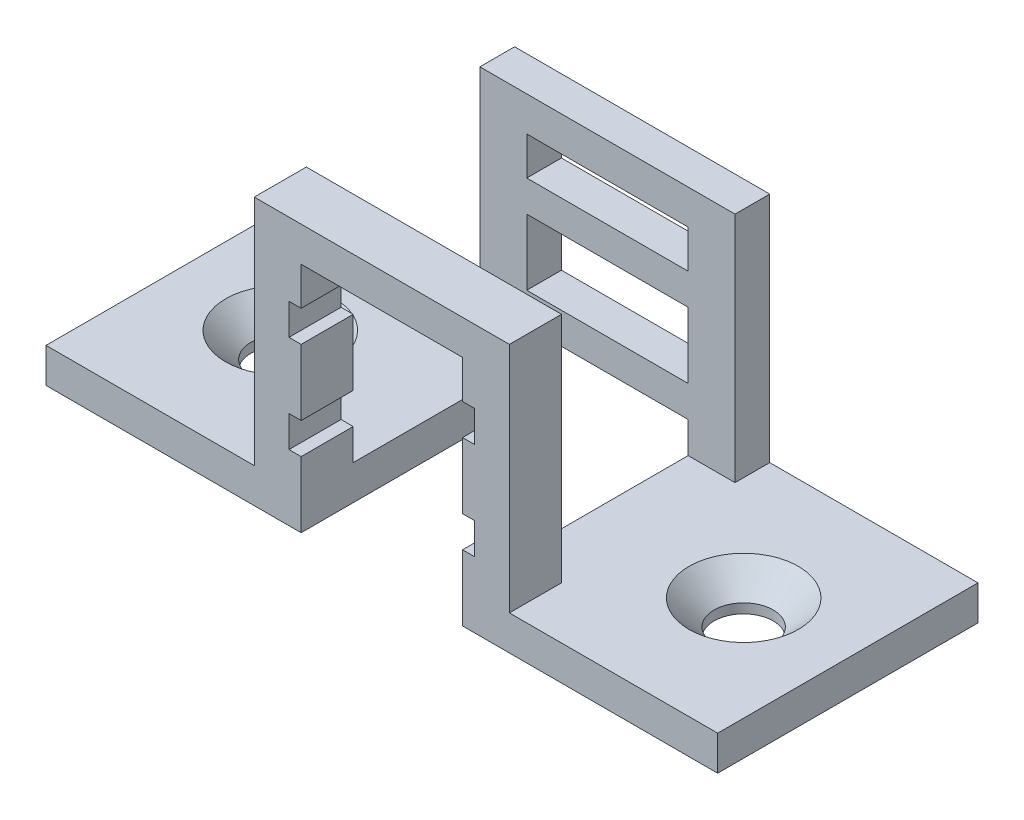
SolidWorks part; units mm, degrees
ref_plane "Front Plane" through (0, 0, 0) normal (0, 0, 1) x (1, 0, 0)
ref_plane "Top Plane" through (0, 0, 0) normal (0, 1, 0) x (1, 0, 0)
ref_plane "Right Plane" through (0, 0, 0) normal (1, 0, 0) x (0, 0, -1)
sketch "Sketch1" plane through (0, 0, 0) normal (0, 1, 0) x (1, 0, 0)
  line L1 (-7.35, -7.5) -> (7.35, -7.5)
  line L2 (-7.35, -7.5) -> (-7.35, 7.5)
  line L3 (-7.35, 7.5) -> (7.35, 7.5)
  line L4 (7.35, -7.5) -> (7.35, 7.5)
  line L5 (-7.35, -7.5) -> (7.35, 7.5) construction
  line L6 (-7.35, 7.5) -> (7.35, -7.5) construction
  point P0 (0, 0)
  dimension "D1" = 15
  dimension "D2" = 14.7
extrude "Boss-Extrude1" add sketch "Sketch1" along normal blind 15.4
sketch "Sketch2" plane through (0, 0, 7.5) normal (0, 0, 1) x (1, 0, 0)
  line L1 (-5.35, -1.2841) -> (5.35, -1.2841)
  line L2 (-5.35, -1.2841) -> (-5.35, 13.4)
  line L3 (-5.35, 13.4) -> (5.35, 13.4)
  line L4 (5.35, -1.2841) -> (5.35, 13.4)
  line L5 (-7.35, 15.4) -> (-7.35, 0) construction
  line L6 (-7.35, 15.4) -> (7.35, 15.4) construction
  line L7 (7.35, 15.4) -> (7.35, 0) construction
  dimension "D1" = 2
  dimension "D2" = 2
  dimension "D3" = 2
  dimension "D4" = 1.2841
extrude "Cut-Extrude1" cut sketch "Sketch2" against normal blind 13
sketch "Sketch4" plane through (0, 0, 7.5) normal (0, 0, 1) x (1, 0, 0)
  line L0 (-7.35, 15.4) -> (-7.35, 0) construction
  line L1 (-7.35, 5.6) -> (-4.65, 5.6)
  line L2 (-7.35, 5.6) -> (-7.35, 9.4)
  line L3 (-7.35, 9.4) -> (-4.65, 9.4)
  line L4 (-4.65, 5.6) -> (-4.65, 9.4)
  line L5 (-7.35, 11.2) -> (-4.65, 11.2)
  line L6 (-7.35, 11.2) -> (-7.35, 15)
  line L7 (-7.35, 15) -> (-4.65, 15)
  line L8 (-4.65, 11.2) -> (-4.65, 15)
  line L14 (0, 0) -> (0, 13.4) construction
  line L15 (-5.35, 0) -> (5.35, 0) construction
  line L16 (5.35, 13.4) -> (-5.35, 13.4) construction
  line L21 (4.65, 11.2) -> (4.65, 15)
  line L22 (7.35, 15) -> (4.65, 15)
  line L23 (7.35, 11.2) -> (7.35, 15)
  line L24 (7.35, 11.2) -> (4.65, 11.2)
  line L25 (4.65, 5.6) -> (4.65, 9.4)
  line L26 (7.35, 9.4) -> (4.65, 9.4)
  line L27 (7.35, 5.6) -> (7.35, 9.4)
  line L28 (7.35, 5.6) -> (4.65, 5.6)
  line L29 (-7.35, 3.8) -> (-4.65, 3.8)
  line L30 (-7.35, 3.8) -> (-7.35, 0)
  line L32 (-7.35, 0) -> (-4.65, 0)
  line L33 (-4.65, 3.8) -> (-4.65, 0)
  line L34 (4.65, 3.8) -> (4.65, 0)
  line L35 (7.35, 0) -> (4.65, 0)
  line L36 (7.35, 3.8) -> (7.35, 0)
  line L37 (7.35, 3.8) -> (4.65, 3.8)
  line L39 (-7.35, 0) -> (-5.35, 0) construction
  dimension "D1" = 3.8
  dimension "D2" = 2.7
  dimension "D3" = 1.8
  dimension "D5" = 3.8
  dimension "D6" = 1.8
extrude "Boss-Extrude2" add sketch "Sketch4" against normal blind 3
sketch "Sketch5" plane through (7.35, 0, 0) normal (1, 0, 0) x (0, 0, -1)
  line L1 (-4.5, 15.4) -> (5.5, 15.4)
  line L2 (-4.5, 15.4) -> (-4.5, 2)
  line L3 (-4.5, 2) -> (5.5, 2)
  line L4 (5.5, 15.4) -> (5.5, 2)
  line L6 (7.5, 15.4) -> (7.5, 0) construction
  line L7 (-7.5, 15.4) -> (-7.5, 0) construction
  line L9 (-7.5, 15.4) -> (7.5, 15.4) construction
  dimension "D1" = 2
  dimension "D2" = 2
  dimension "D3" = 3
extrude "Cut-Extrude2" cut sketch "Sketch5" against normal through all
sketch "Sketch6" plane through (0, 0, 7.5) normal (0, 0, 1) x (1, 0, 0)
  line L9 (-4.65, 9.4) -> (4.65, 9.4)
  line L10 (-4.65, 9.4) -> (-4.65, 5.6)
  line L11 (-4.65, 5.6) -> (4.65, 5.6)
  line L12 (4.65, 9.4) -> (4.65, 5.6)
  line L13 (-4.65, 3.8) -> (4.65, 3.8)
  line L14 (-4.65, 3.8) -> (-4.65, 0)
  line L15 (-4.65, 0) -> (4.65, 0)
  line L16 (4.65, 3.8) -> (4.65, 0)
  line L19 (4.65, 0) -> (7.35, 0) construction
  line L20 (4.65, 13.4) -> (4.65, 11.2) construction
  line L21 (-4.65, 13.4) -> (4.65, 13.4)
  line L22 (-4.65, 13.4) -> (-4.65, 11.2)
  line L23 (-4.65, 11.2) -> (4.65, 11.2)
  line L24 (4.65, 13.4) -> (4.65, 11.2)
  line L25 (4.65, 11.2) -> (5.35, 11.2) construction
extrude "Cut-Extrude3" cut sketch "Sketch6" against normal through all
sketch "Sketch7" plane through (-7.35, 0, 0) normal (-1, 0, 0) x (0, 0, 1)
  line L0 (-7.5, 0) -> (7.5, 0) construction
  line L1 (-7.5, 2) -> (7.5, 2)
  line L2 (-7.5, 2) -> (-7.5, 0)
  line L3 (-7.5, 0) -> (7.5, 0)
  line L4 (7.5, 2) -> (7.5, 0)
  line L5 (-7.5, 15.4) -> (-7.5, 0) construction
  line L6 (7.5, 15.4) -> (7.5, 0) construction
  point P4 (0, 0)
  point P7 (0, 0)
  dimension "D1" = 2
extrude "Boss-Extrude3" add sketch "Sketch7" along normal blind 12 and the other way blind 2.7
sketch "Sketch8" plane through (7.35, 0, 0) normal (1, 0, 0) x (0, 0, -1)
  line L0 (-7.5, 0) -> (7.5, 0) construction
  line L1 (-7.5, 2) -> (7.5, 2)
  line L2 (-7.5, 2) -> (-7.5, 0)
  line L3 (-7.5, 0) -> (7.5, 0)
  line L4 (7.5, 2) -> (7.5, 0)
  line L5 (-7.5, 15.4) -> (-7.5, 0) construction
  point P4 (7.5, 2)
  point P7 (-7.5, 2)
extrude "Boss-Extrude4" add sketch "Sketch8" along normal blind 12 and the other way blind 2.7
sketch "Sketch9" plane through (0, 2, 0) normal (0, 1, 0) x (1, 0, 0)
  line L0 (-19.35, 0) -> (-4.65, 0) construction
  line L1 (-19.35, -7.5) -> (-19.35, 7.5) construction
  line L3 (-13.35, 7.5) -> (-13.35, -7.5) construction
  line L4 (-7.35, 7.5) -> (-19.35, 7.5) construction
  line L5 (-7.35, -7.5) -> (-19.35, -7.5) construction
  point P5 (-13.35, 0)
hole_wizard "CSK for M3 Flat Head Machine Screw1" positions "Sketch9" profile "Sketch10" countersink size "M3" standard "ANSI Metric" end condition through all
sketch "Sketch10" plane through (-13.35, 2, 0) normal (1, 0, 0) x (0, 0, 1)
  line L0 (0, 0) -> (0, 2)
  line L1 (0, 2) -> (1.7, 2)
  line L2 (1.7, 2) -> (1.7, 1.45)
  line L3 (1.7, 1.45) -> (3.15, 0)
  line L5 (3.15, 0) -> (0, 0)
  line L6 (-1.7, 1.45) -> (-3.15, 0) construction
  line L11 (0, -6.35) -> (0, 107.95) construction
  dimension "Thru Hole Dia." = 3.4
  dimension "Thru Hole Depth" = 2
  dimension "Near C'Sink Dia." = 6.3
  dimension "Near C'Sink Angle" = 90
sketch "Sketch11" plane through (0, 2, 0) normal (0, 1, 0) x (1, 0, 0)
  line L0 (13.35, 7.5) -> (13.35, -7.5) construction
  line L1 (7.35, 7.5) -> (19.35, 7.5) construction
  line L2 (7.35, -7.5) -> (19.35, -7.5) construction
  line L3 (19.35, 0) -> (4.65, 0) construction
  line L4 (19.35, 7.5) -> (19.35, -7.5) construction
  line L5 (4.65, 5.5) -> (4.65, -4.5) construction
  point P13 (13.35, 0)
hole_wizard "CSK for M3 Flat Head Machine Screw2" positions "Sketch11" profile "Sketch12" countersink size "M3" standard "ANSI Metric" end condition through all
sketch "Sketch12" plane through (13.35, 2, 0) normal (1, 0, 0) x (0, 0, 1)
  line L0 (0, 0) -> (0, 2)
  line L1 (0, 2) -> (1.7, 2)
  line L2 (1.7, 2) -> (1.7, 1.45)
  line L3 (1.7, 1.45) -> (3.15, 0)
  line L5 (3.15, 0) -> (0, 0)
  line L6 (-1.7, 1.45) -> (-3.15, 0) construction
  line L11 (0, -6.35) -> (0, 107.95) construction
  dimension "Thru Hole Dia." = 3.4
  dimension "Thru Hole Depth" = 2
  dimension "Near C'Sink Dia." = 6.3
  dimension "Near C'Sink Angle" = 90
